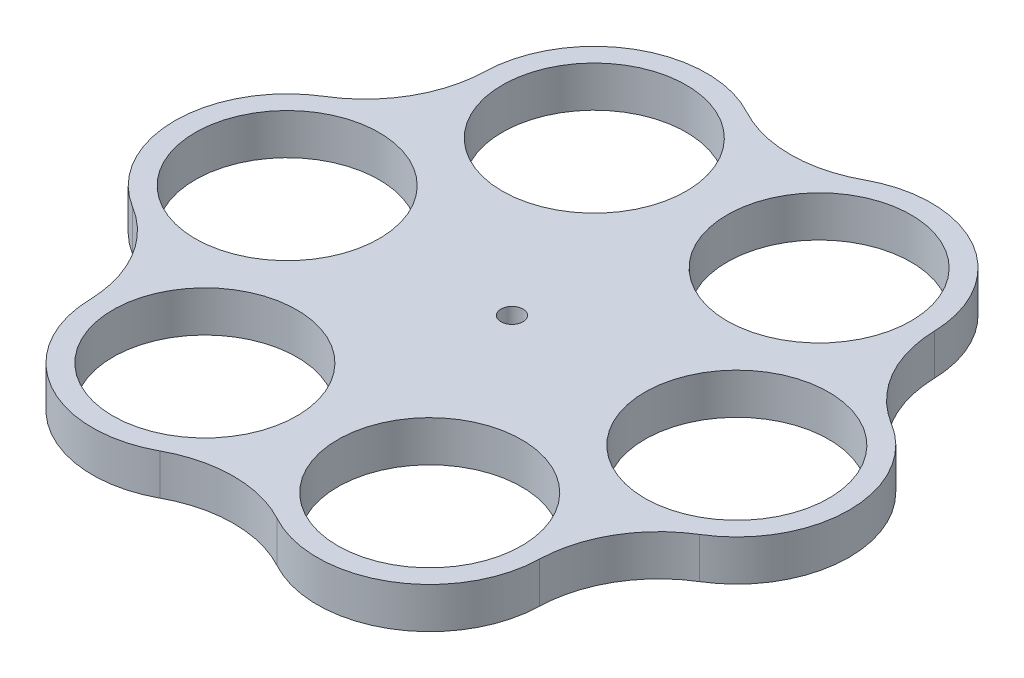
SolidWorks part; units mm, degrees
ref_plane "Front Plane" through (0, 0, 0) normal (0, 0, 1) x (1, 0, 0)
ref_plane "Top Plane" through (0, 0, 0) normal (0, 1, 0) x (1, 0, 0)
ref_plane "Right Plane" through (0, 0, 0) normal (1, 0, 0) x (0, 0, -1)
sketch "Sketch1" plane through (0, 0, 0) normal (0, 1, 0) x (1, 0, 0)
  line L3 (-27.5, 0) -> (-32.5, 0)
  circle A0 centre (27.5, 47.6314) radius 22.5
  circle A1 centre (-27.5, 47.6314) radius 22.5
  circle A2 centre (-55, 0) radius 22.5
  circle A3 centre (-27.5, -47.6314) radius 22.5
  circle A4 centre (27.5, -47.6314) radius 22.5
  circle A5 centre (55, 0) radius 22.5
  arc A6 (54.9915, 48.3168) -> (14.3478, 71.7824) centre (27.5, 47.6314) ccw
  arc A7 (-14.3478, 71.7824) -> (-54.9915, 48.3168) centre (-27.5, 47.6314) ccw
  arc A8 (-69.3393, 23.4656) -> (-69.3393, -23.4656) centre (-55, 0) ccw
  arc A9 (-54.9915, -48.3168) -> (-14.3478, -71.7824) centre (-27.5, -47.6314) ccw
  arc A10 (14.3478, -71.7824) -> (54.9915, -48.3168) centre (27.5, -47.6314) ccw
  arc A11 (69.3393, -23.4656) -> (69.3393, 23.4656) centre (55, 0) ccw
  arc A12 (54.9915, 48.3168) -> (69.3393, 23.4656) centre (84.9821, 49.0645) ccw
  arc A13 (-14.3478, 71.7824) -> (14.3478, 71.7824) centre (0, 98.1289) ccw
  arc A14 (-69.3393, 23.4656) -> (-54.9915, 48.3168) centre (-84.9821, 49.0645) ccw
  arc A15 (-54.9915, -48.3168) -> (-69.3393, -23.4656) centre (-84.9821, -49.0645) ccw
  arc A16 (14.3478, -71.7824) -> (-14.3478, -71.7824) centre (0, -98.1289) ccw
  arc A17 (69.3393, -23.4656) -> (54.9915, -48.3168) centre (84.9821, -49.0645) ccw
  circle A18 centre (0, 0) radius 2.7
extrude "Boss-Extrude1" add sketch "Sketch1" along normal blind 10 contours A17 A11 A12 A6 A13 A7 A14 A8 A15 A9 A16 A10 A18 A5 A4 A3 A1 A0 A2 region at (57.0687, 0, -32.9486)
